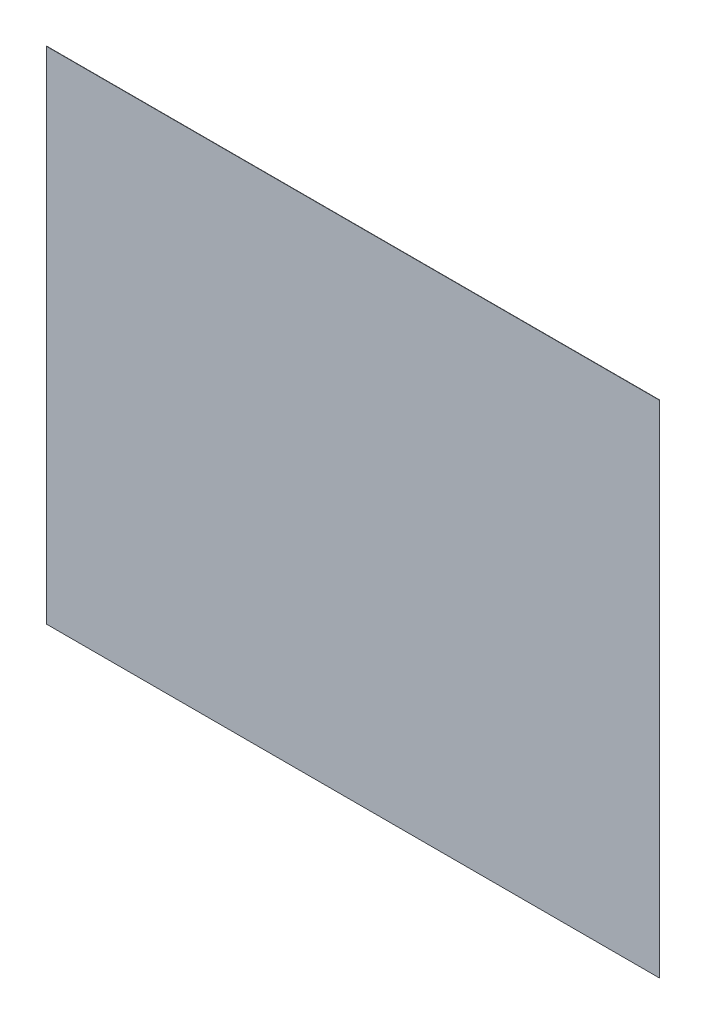
SolidWorks part; units mm, degrees
ref_plane "Front Plane" through (0, 0, 0) normal (0, 0, 1) x (1, 0, 0)
ref_plane "Top Plane" through (0, 0, 0) normal (0, 1, 0) x (1, 0, 0)
ref_plane "Right Plane" through (0, 0, 0) normal (1, 0, 0) x (0, 0, -1)
sketch "Sketch1" plane through (0, 0, 0) normal (0, 0, 1) x (1, 0, 0)
  line L1 (0, 0) -> (1991, 0)
  line L2 (0, 0) -> (0, 1625)
  line L3 (0, 1625) -> (1991, 1625)
  line L4 (1991, 0) -> (1991, 1625)
  dimension "D1" = 1991
  dimension "D2" = 1625
extrude "Boss-Extrude1" add sketch "Sketch1" along normal blind 1
